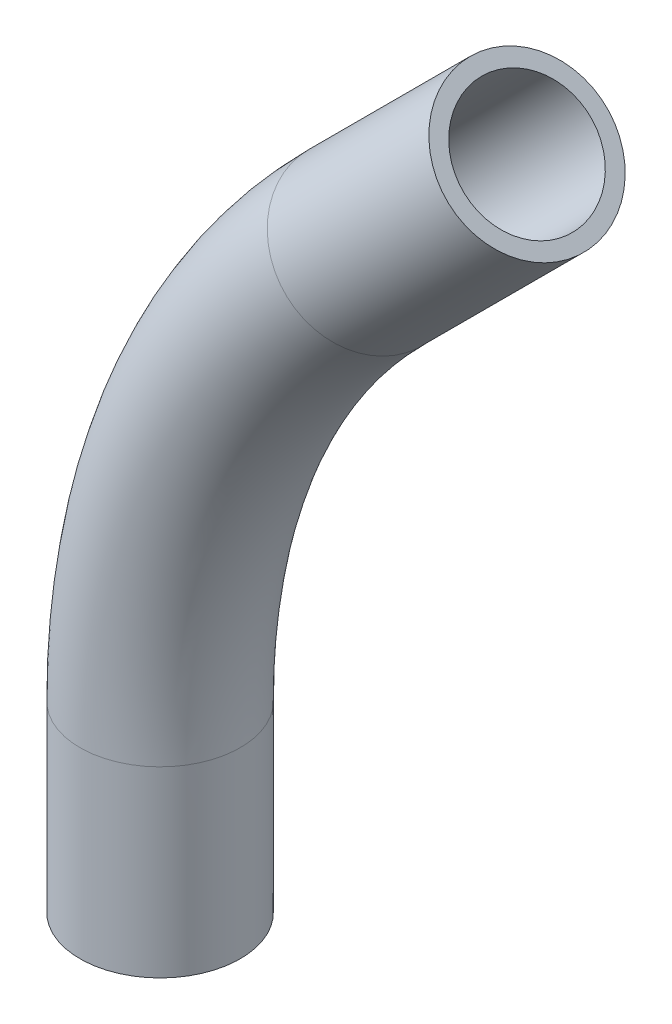
SolidWorks part; units mm, degrees
material "PVC Rigid"
ref_plane "front" through (0, 0, 0) normal (0, 0, 1) x (1, 0, 0)
ref_plane "top" through (0, 0, 0) normal (0, 1, 0) x (1, 0, 0)
ref_plane "side" through (0, 0, 0) normal (1, 0, 0) x (0, 0, -1)
sketch "ElbowArc" plane through (0, 0, 0) normal (0, 0, 1) x (1, 0, 0)
  arc A0 (-146.05, 0) -> (-103.2729, 103.2729) centre (0, 0) cw
  dimension "BendAngle" = 45
  dimension "BendRadius" = 146.05
sketch "Route" plane through (0, 0, 0) normal (0, 1, 0) x (1, 0, 0)
  circle A0 centre (-146.05, 0) radius 16.7005
  dimension "ElbowOD" = 33.401
  dimension "BendRadius" = 146.05
sweep "Elbow" add profiles "Route" path "ElbowArc"
sketch3d "3DSketch2"
  circle A0 centre (-146.05, 0, 0) radius 16.7005 construction
  circle A1 centre (-103.2729, 103.2729, 0) radius 16.7005 construction
  point P0 (-146.05, 0, 0)
  point P3 (-146.05, 16.7005, 0)
  point P4 (-103.2729, 103.2729, 0)
  point P7 (-91.4639, 115.082, 0)
other "CPoint1" parameters "Diameter"=25.4, "StubLength"=0
ref_axis "Axis4" through (-146.05, -10, 0) along (0, 1, 0)
other "CPoint2" parameters "Diameter"=25.4, "StubLength"=0
ref_axis "Axis5" through (-96.2019, 110.344, 0) along (-0.7071, -0.7071, 0)
other "RPoint1"
shell "ElbowShell" thickness 3.3782 removed face at (-103.2729, 103.2729, 16.7005) removed face at (-146.05, 0, 16.7005)
sketch "Sketch2" plane through (0, 0, 0) normal (0.7071, 0.7071, 0) x (0, 0, -1)
  circle A0 centre (0, 146.05) radius 16.7005 construction
  circle A1 centre (0, 146.05) radius 13.3223 construction
  circle A2 centre (0, 146.05) radius 16.7005
  circle A3 centre (0, 146.05) radius 13.3223
extrude "ElbowExtension-Extrude1" add sketch "Sketch2" along normal blind 47.625
sketch "Sketch3" plane through (0, 0, 0) normal (0, -1, 0) x (1, 0, 0)
  circle A0 centre (-146.05, 0) radius 13.3223 construction
  circle A1 centre (-146.05, 0) radius 16.7005 construction
  circle A2 centre (-146.05, 0) radius 13.3223
  circle A3 centre (-146.05, 0) radius 16.7005
extrude "ElbowExtension-Extrude2" add sketch "Sketch3" along normal blind 38.1
sketch "Sketch4" plane through (33.676, 33.676, 0) normal (0.7071, 0.7071, 0) x (0, 0, -1)
  point P0 (0, 101.6)
